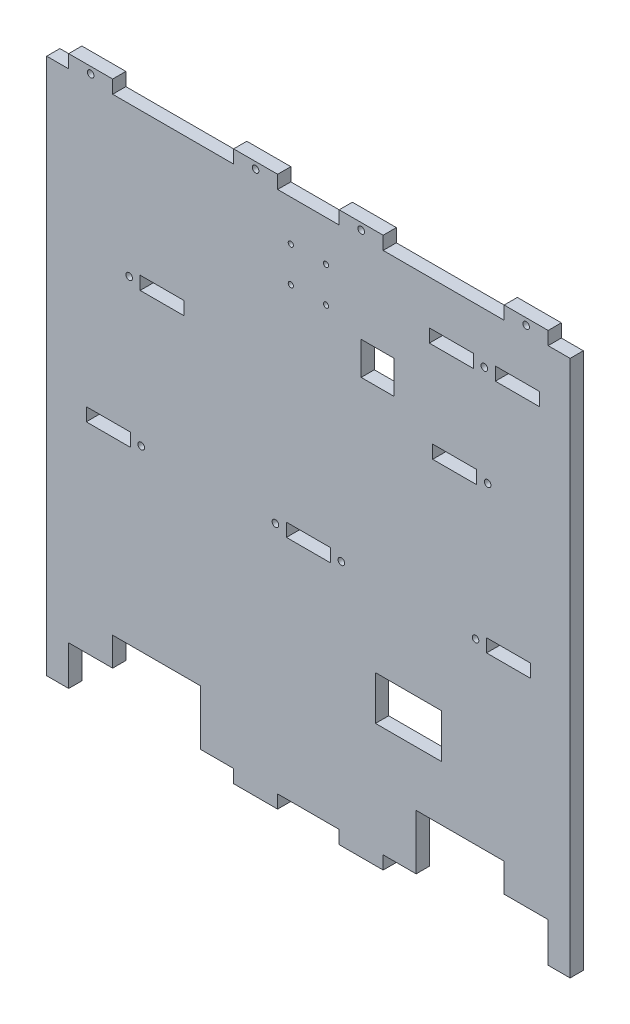
SolidWorks part; units mm, degrees
ref_plane "Plan de face" through (0, 0, 0) normal (0, 0, 1) x (1, 0, 0)
ref_plane "Plan de dessus" through (0, 0, 0) normal (0, 1, 0) x (1, 0, 0)
ref_plane "Plan de droite" through (0, 0, 0) normal (1, 0, 0) x (0, 0, -1)
sketch "Esquisse1" plane through (0, 0, 0) normal (0, 0, 1) x (1, 0, 0)
  line L0 (0, 139.6766) -> (0, -178.3461) construction
  line L1 (-109, 119) -> (109, 119)
  line L2 (-109, 119) -> (-109, -119)
  line L3 (-109, -119) -> (109, -119)
  line L4 (109, 119) -> (109, -119)
  line L5 (-101, -16) -> (-81, -16)
  line L6 (-101, -16) -> (-101, -10)
  line L7 (-101, -10) -> (-81, -10)
  line L8 (-81, -16) -> (-81, -10)
  line L9 (-10, -16) -> (10, -16)
  line L10 (-10, -16) -> (-10, -10)
  line L11 (-10, -10) -> (10, -10)
  line L12 (10, -16) -> (10, -10)
  line L13 (81, -16) -> (101, -16)
  line L14 (81, -16) -> (81, -10)
  line L15 (81, -10) -> (101, -10)
  line L16 (101, -16) -> (101, -10)
  line L17 (-76.5, 54) -> (-56.5, 54)
  line L18 (-76.5, 54) -> (-76.5, 48)
  line L19 (-76.5, 48) -> (-56.5, 48)
  line L20 (-56.5, 54) -> (-56.5, 48)
  line L21 (56.5, 54) -> (76.5, 54)
  line L22 (56.5, 54) -> (56.5, 48)
  line L23 (56.5, 48) -> (76.5, 48)
  line L24 (76.5, 54) -> (76.5, 48)
  line L25 (30.5, -69) -> (60.5, -69)
  line L26 (30.5, -69) -> (30.5, -49)
  line L27 (30.5, -49) -> (60.5, -49)
  line L28 (60.5, -69) -> (60.5, -49)
  line L30 (55, 99) -> (75, 99)
  line L31 (55, 99) -> (55, 93)
  line L32 (55, 93) -> (75, 93)
  line L33 (75, 99) -> (75, 93)
  line L34 (85, 99) -> (105, 99)
  line L35 (85, 99) -> (85, 93)
  line L36 (85, 93) -> (105, 93)
  line L37 (105, 99) -> (105, 93)
  line L38 (24, 64) -> (39, 64)
  line L39 (24, 64) -> (24, 79)
  line L40 (24, 79) -> (39, 79)
  line L41 (39, 64) -> (39, 79)
  dimension "D1" = 238
  dimension "D2" = 218
  dimension "D3" = 109
  dimension "D4" = 119
  dimension "D5" = 20
  dimension "D6" = 6
  dimension "D7" = 6
  dimension "D8" = 20
  dimension "D9" = 20
  dimension "D10" = 6
  dimension "D11" = 103
  dimension "D12" = 8
  dimension "D13" = 8
  dimension "D14" = 99
  dimension "D15" = 103
  dimension "D16" = 103
  dimension "D17" = 20
  dimension "D18" = 6
  dimension "D19" = 6
  dimension "D20" = 20
  dimension "D21" = 167
  dimension "D22" = 167
  dimension "D23" = 32.5
  dimension "D24" = 32.5
  dimension "D25" = 20
  dimension "D26" = 30
  dimension "D27" = 50
  dimension "D28" = 20.5
  dimension "D29" = 6
  dimension "D30" = 6
  dimension "D31" = 20
  dimension "D32" = 20
  dimension "D33" = 20
  dimension "D34" = 20
  dimension "D35" = 10
  dimension "D36" = 4
  dimension "D37" = 15
  dimension "D38" = 15
  dimension "D39" = 70
  dimension "D40" = 40
extrude "Boss.-Extru.1" add sketch "Esquisse1" along normal blind 6
sketch "Esquisse2" plane through (0, 0, 6) normal (0, 0, 1) x (1, 0, 0)
  line L0 (-109, -119) -> (109, -119) construction
  line L1 (-89, -119) -> (-49, -119)
  line L2 (-89, -119) -> (-89, -94)
  line L3 (-89, -94) -> (-49, -94)
  line L4 (-49, -119) -> (-49, -94)
  line L5 (-109, 119) -> (-109, -119) construction
  line L6 (49, -119) -> (89, -119)
  line L7 (49, -119) -> (49, -94)
  line L8 (49, -94) -> (89, -94)
  line L9 (89, -119) -> (89, -94)
  line L10 (109, -119) -> (109, 119) construction
  dimension "D1" = 40
  dimension "D2" = 20
  dimension "D3" = 40
  dimension "D4" = 20
  dimension "D5" = 25
  dimension "D6" = 25
extrude "Enlèv. mat.-Extru.1" cut sketch "Esquisse2" against normal blind 6
sketch "Esquisse3" plane through (0, 0, 6) normal (0, 0, 1) x (1, 0, 0)
  line L0 (0, 157.5653) -> (0, -190.6765) construction
  line L5 (-49, -119) -> (49, -119) construction
  line L6 (-34, -119) -> (-14, -119)
  line L7 (-34, -119) -> (-34, -125)
  line L8 (-34, -125) -> (-14, -125)
  line L9 (-14, -119) -> (-14, -125)
  line L10 (-49, -119) -> (-49, -94) construction
  line L15 (14, -119) -> (14, -125)
  line L16 (34, -125) -> (14, -125)
  line L17 (34, -119) -> (34, -125)
  line L18 (34, -119) -> (14, -119)
  line L19 (198.2674, 0) -> (-212.4835, 0) construction
  line L20 (0, -157.5653) -> (0, 190.6765) construction
  line L21 (34, 125) -> (14, 125)
  line L22 (14, 119) -> (14, 125)
  line L23 (89, 125) -> (109, 125)
  line L24 (89, 125) -> (89, 119)
  line L25 (89, 119) -> (109, 119)
  line L26 (109, 125) -> (109, 119)
  line L27 (-14, 119) -> (-14, 125)
  line L28 (-34, 125) -> (-14, 125)
  line L29 (-34, 119) -> (-34, 125)
  line L30 (-34, 119) -> (-14, 119)
  line L31 (-109, 125) -> (-109, 119)
  line L32 (-89, 119) -> (-109, 119)
  line L33 (-89, 125) -> (-89, 119)
  line L34 (-89, 125) -> (-109, 125)
  line L35 (34, 119) -> (14, 119)
  line L36 (34, 119) -> (34, 125)
  dimension "D2" = 20
  dimension "D3" = 6
  dimension "D4" = 15
extrude "Boss.-Extru.3" add sketch "Esquisse3" against normal blind 6
sketch "Esquisse4" plane through (0, 0, 6) normal (0, 0, 1) x (1, 0, 0)
  line L0 (-111.0944, 51) -> (126.4062, 51) construction
  line L1 (116.6655, -13) -> (-122.9189, -13) construction
  line L2 (76.5, 48) -> (76.5, 54) construction
  line L3 (0, 153.5677) -> (0, -173.1111) construction
  line L4 (45.0686, 96) -> (109.1297, 96) construction
  line L5 (81, -10) -> (81, -16) construction
  line L6 (10, -16) -> (10, -10) construction
  line L7 (-10, -10) -> (-10, -16) construction
  line L8 (75, 93) -> (75, 99) construction
  line L9 (-114.2336, 122) -> (-6.2018, 122) construction
  line L10 (-56.5, 54) -> (-76.5, 54) construction
  line L11 (-89, 125) -> (-109, 125) construction
  line L12 (-34, 125) -> (-34, 119) construction
  line L13 (55, 93) -> (75, 93) construction
  line L14 (-89, 119) -> (-89, 125) construction
  line L15 (-81, -10) -> (-101, -10) construction
  circle A0 centre (-15, -13) radius 1.5
  circle A1 centre (-76, -13) radius 1.5
  circle A2 centre (80, 96) radius 1.5
  circle A3 centre (81.5, 51) radius 1.5
  circle A4 centre (76, -13) radius 1.5
  circle A5 centre (15, -13) radius 1.5
  circle A6 centre (-81.5, 51) radius 1.5
  circle A7 centre (-99, 122) radius 1.5
  circle A8 centre (-24, 122) radius 1.5
  circle A9 centre (24, 122) radius 1.5
  circle A10 centre (99, 122) radius 1.5
  dimension "D2" = 5
  dimension "D3" = 3
  dimension "D4" = 3
  dimension "D5" = 5
  dimension "D6" = 5
  dimension "D7" = 3
  dimension "D8" = 3
  dimension "D9" = 3
  dimension "D10" = 5
  dimension "D11" = 3
  dimension "D12" = 5
  dimension "D13" = 3
  dimension "D15" = 3
  dimension "D16" = 3
  dimension "D17" = 10
  dimension "D18" = 10
  dimension "D19" = 3
  dimension "D14" = 3
extrude "Enlèv. mat.-Extru.2" cut sketch "Esquisse4" against normal blind 6
sketch "Esquisse5" plane through (0, 0, 6) normal (0, 0, 1) x (1, 0, 0)
  line L0 (-109, 119) -> (-109, -125)
  line L1 (-109, 119) -> (-119, 119)
  line L2 (-109, -125) -> (-119, -125)
  line L3 (-119, 119) -> (-119, -125)
  line L5 (109, -125) -> (109, 119)
  line L6 (109, -125) -> (119, -125)
  line L7 (109, 119) -> (119, 119)
  line L8 (119, -125) -> (119, 119)
  line L11 (109, 125) -> (89, 125) construction
  line L12 (-89, 125) -> (-109, 125) construction
  dimension "D1" = 10
  dimension "D2" = 10
  dimension "D3" = 244
  dimension "D4" = 244
  dimension "D5" = 6
  dimension "D6" = 6
extrude "Boss.-Extru.4" add sketch "Esquisse5" against normal blind 6
sketch "Esquisse6" plane through (0, 0, 6) normal (0, 0, 1) x (1, 0, 0)
  line L0 (0, 108.4917) -> (0, -172.5759) construction
  line L1 (89, -119) -> (109, -119)
  line L2 (89, -119) -> (89, -107)
  line L3 (89, -107) -> (109, -107)
  line L4 (109, -119) -> (109, -107)
  line L5 (-109, -119) -> (-109, -107)
  line L6 (-89, -107) -> (-109, -107)
  line L7 (-89, -119) -> (-89, -107)
  line L8 (-89, -119) -> (-109, -119)
  dimension "D1" = 12
  dimension "D2" = 20
extrude "Enlèv. mat.-Extru.3" cut sketch "Esquisse6" against normal blind 6
sketch "Esquisse7" plane through (0, 0, 6) normal (0, 0, 1) x (1, 0, 0)
  line L0 (14, 119) -> (-14, 119) construction
  line L1 (14, 125) -> (14, 119) construction
  circle A0 centre (-8, 100.5) radius 1.175
  circle A1 centre (8, 100.5) radius 1.175
  circle A2 centre (-8, 84.5) radius 1.175
  circle A3 centre (8, 84.5) radius 1.175
  dimension "D1" = 16
  dimension "D7" = 2.35
  dimension "D8" = 2.35
  dimension "D9" = 2.35
  dimension "D10" = 2.35
  dimension "D2" = 16
  dimension "D3" = 16
  dimension "D4" = 16
  dimension "D5" = 18.5
  dimension "D6" = 6
  dimension "D11" = 18.5
extrude "Enlèv. mat.-Extru.4" cut sketch "Esquisse7" against normal through all
equation "\"D3@Esquisse1\"=\"D2@Esquisse1\"/2"
equation "\"D4@Esquisse1\"=\"D1@Esquisse1\"/2"
